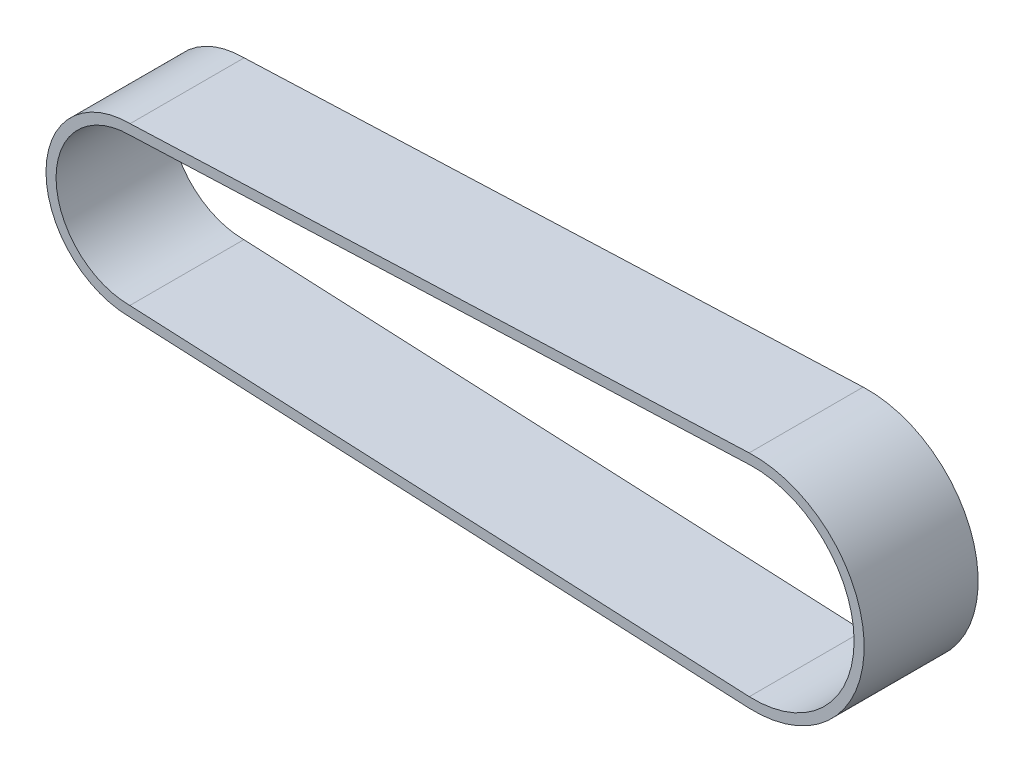
SolidWorks part; units mm, degrees
material "Rubber"
ref_plane "Front Plane" through (0, 0, 0) normal (0, 0, 1) x (1, 0, 0)
ref_plane "Top Plane" through (0, 0, 0) normal (0, 1, 0) x (1, 0, 0)
ref_plane "Right Plane" through (0, 0, 0) normal (1, 0, 0) x (0, 0, -1)
sketch "Sketch1" plane through (0, 0, 0) normal (0, 0, 1) x (1, 0, 0)
  line L0 (0.0677, 10.9998) -> (92.4086, 14.6392)
  line L5 (92.369, -15.3359) -> (0, -11)
  line L6 (0.0416, 12.4999) -> (92.3495, 16.138)
  line L7 (92.3022, -16.8345) -> (-0.0363, -12.4999)
  arc A4 (0.0677, 10.9998) -> (0, -11) centre (0, 0) ccw
  arc A5 (92.369, -15.3359) -> (92.4086, 14.6392) centre (92.9993, -0.3492) ccw
  arc A6 (92.3022, -16.8345) -> (92.3495, 16.138) centre (92.9993, -0.3492) ccw
  arc A7 (0.0416, 12.4999) -> (-0.0363, -12.4999) centre (0, 0) ccw
  point P6 (84.9994, 29.0514)
  dimension "D1" = 93
  dimension "D2" = 15
  dimension "D3" = 11
  dimension "D4" = 1.5
extrude "Boss-Extrude1" add sketch "Sketch1" along normal blind 17
